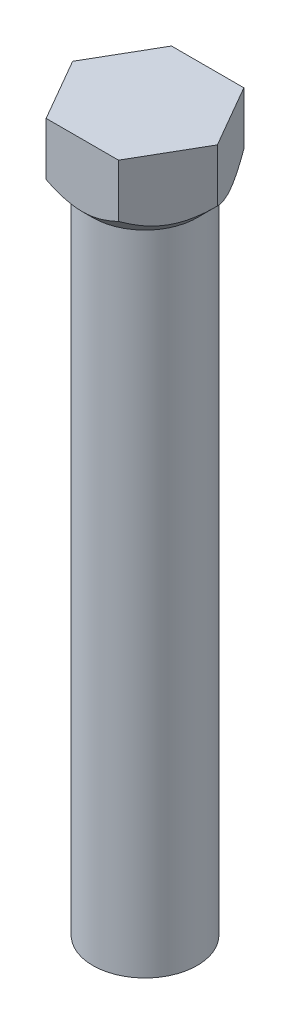
SolidWorks part; units mm, degrees
ref_plane "Front Plane" through (0, 0, 0) normal (0, 0, 1) x (1, 0, 0)
ref_plane "Top Plane" through (0, 0, 0) normal (0, 1, 0) x (1, 0, 0)
ref_plane "Right Plane" through (0, 0, 0) normal (1, 0, 0) x (0, 0, -1)
sketch "Sketch1" plane through (0, 0, 0) normal (0, 1, 0) x (1, 0, 0)
  circle A0 centre (0, 0) radius 2.5
  dimension "D1" = 5
extrude "Boss-Extrude1" add sketch "Sketch1" along normal blind 32
sketch "Sketch2" plane through (0, 32, 0) normal (0, 1, 0) x (1, 0, 0)
  line L1 (3.4641, 0) -> (1.7321, 3)
  line L2 (1.7321, 3) -> (-1.7321, 3)
  line L3 (-1.7321, 3) -> (-3.4641, 0)
  line L4 (-3.4641, 0) -> (-1.7321, -3)
  line L5 (-1.7321, -3) -> (1.7321, -3)
  line L6 (1.7321, -3) -> (3.4641, 0)
  circle A0 centre (0, 0) radius 3 construction
  dimension "D1" = 6
extrude "Boss-Extrude2" add sketch "Sketch2" along normal blind 2.5
chamfer "Chamfer2" distance 1 angle 45 1 edges at (0, 32, 2.5)
